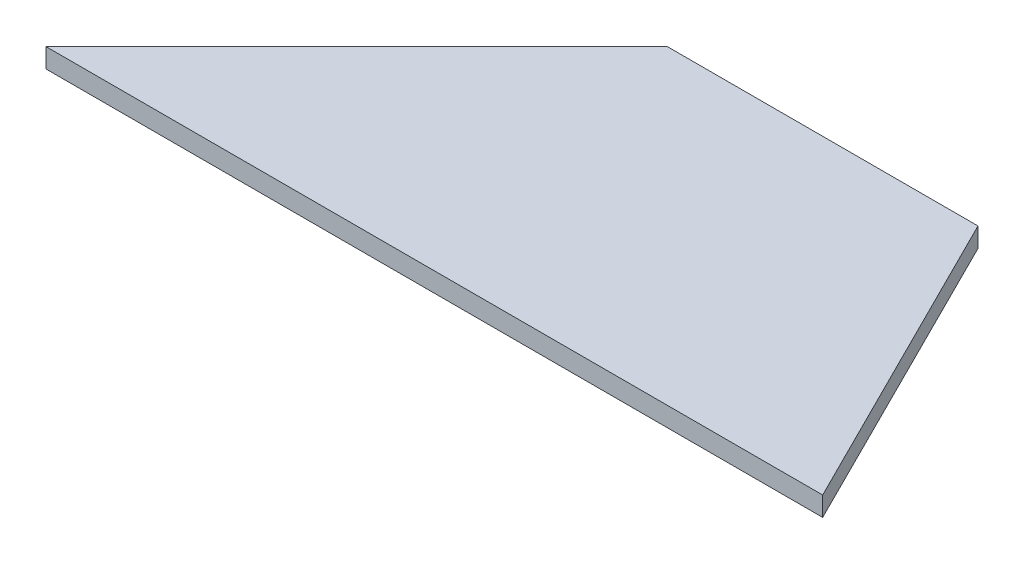
SolidWorks part; units mm, degrees
ref_plane "Front Plane" through (0, 0, 0) normal (0, 0, 1) x (1, 0, 0)
ref_plane "Top Plane" through (0, 0, 0) normal (0, 1, 0) x (1, 0, 0)
ref_plane "Right Plane" through (0, 0, 0) normal (1, 0, 0) x (0, 0, -1)
sketch "Sketch2" plane through (0, 0, 0) normal (0, 1, 0) x (1, 0, 0)
  line L3 (254, 0) -> (203.2, 101.6)
  line L4 (203.2, 101.6) -> (101.6, 101.6)
  line L5 (101.6, 101.6) -> (0, 0)
  line L8 (0, 0) -> (254, 0)
  point P0 (0, 0)
  dimension "D1" = 254
  dimension "D2" = 101.6
  dimension "D3" = 101.6
  dimension "D7" = 101.6
extrude "Boss-Extrude1" add sketch "Sketch2" along normal blind 6.35
